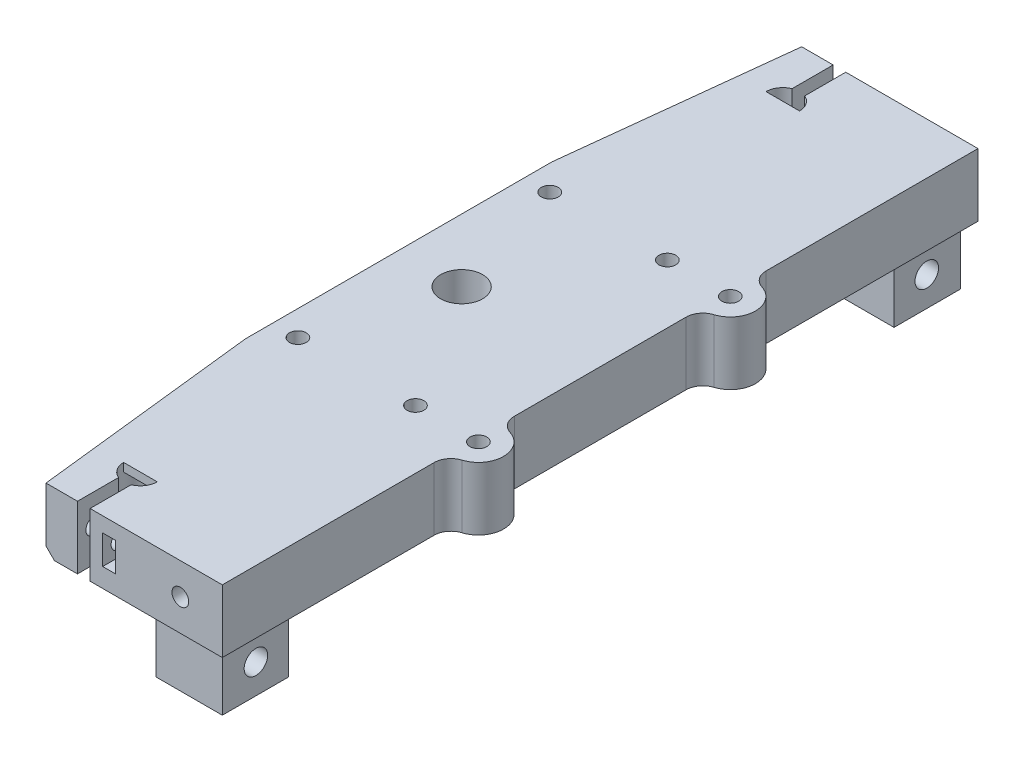
SolidWorks part; units mm, degrees
ref_plane "Płaszczyzna przednia" through (0, 0, 0) normal (0, 0, 1) x (1, 0, 0)
ref_plane "Płaszczyzna górna" through (0, 0, 0) normal (0, 1, 0) x (1, 0, 0)
ref_plane "Płaszczyzna prawa" through (0, 0, 0) normal (1, 0, 0) x (0, 0, -1)
sketch "Szkic1" plane through (0, 0, 0) normal (0, 1, 0) x (1, 0, 0)
  line L0 (-20.5, 36.5) -> (-14.5, 90)
  line L1 (27.5, -90) -> (-14.5, -90)
  line L2 (27.5, -90) -> (27.5, 90)
  line L3 (27.5, 90) -> (-14.5, 90)
  line L4 (-20.5, -36.5) -> (-20.5, 36.5)
  line L5 (27.5, 0) -> (-46.9742, 0) construction
  line L6 (-7, -80.2081) -> (-7, -90)
  line L7 (-20.5, -36.5) -> (-14.5, -90)
  line L8 (-4, -80.2081) -> (-4, -90)
  line L9 (-7, 80.2081) -> (-7, 90)
  line L10 (-4, 80.2081) -> (-4, 90)
  circle A0 centre (-14.5, 30) radius 2
  circle A1 centre (13.5, 30) radius 2
  circle A4 centre (13.5, -30) radius 2
  circle A5 centre (-14.5, -30) radius 2
  circle A6 centre (-5.5, -76.5) radius 4
  circle A7 centre (-5.5, 0) radius 5
  circle A8 centre (-5.5, 76.5) radius 4
  point P0 (0, 0)
  dimension "D7" = 6
  dimension "D10" = 4
  dimension "D11" = 30
  dimension "D12" = 15
  dimension "D13" = 10
  dimension "D16" = 8
  dimension "D1" = 48
  dimension "D2" = 180
  dimension "D3" = 27.5
  dimension "D4" = 90
  dimension "D5" = 42
  dimension "D6" = 73
  dimension "D8" = 28
  dimension "D14" = 13.5
  dimension "D15" = 15
  dimension "D17" = 3
  dimension "D19" = 13.5
  dimension "D20" = 3
extrude "Dodanie-wyciągnięcie1" add sketch "Szkic1" along normal blind 15 contours L2 L5 A7 L4 L7 L1 L6 A6 L8 A5 A4 | L5 L2 L3 L10 A8 L9 L0 L4 A7 A0 A1 region at (4.6694, 0, -43.745) region at (4.6694, 0, 43.745)
sketch "Szkic2" plane through (0, 0, 0) normal (0, -1, 0) x (1, 0, 0)
  line L0 (27.5, 90) -> (27.5, -90) construction
  line L1 (25.4, -87.9) -> (9.6, -87.9)
  line L2 (25.4, -87.9) -> (25.4, -72.1)
  line L3 (25.4, -72.1) -> (9.6, -72.1)
  line L4 (9.6, -87.9) -> (9.6, -72.1)
  line L5 (25.4, -87.9) -> (9.6, -72.1) construction
  line L6 (25.4, -72.1) -> (9.6, -87.9) construction
  line L7 (27.5, -90) -> (-4, -90) construction
  point P0 (17.5, -80)
  dimension "D1" = 15.8
  dimension "D2" = 2.1
  dimension "D3" = 2.1
extrude "Dodanie-wyciągnięcie2" add sketch "Szkic2" along normal blind 14
mirror "Lustro1" about plane through (0, 0, 0) normal (0, 0, 1) of "Dodanie-wyciągnięcie2"
sketch "Szkic3" plane through (0, 15, 0) normal (0, 1, 0) x (1, 0, 0)
  line L0 (-9.5, 76.5) -> (-1.5, 76.5)
  line L1 (-9.5, -76.5) -> (-1.5, -76.5)
  arc A0 (-7, 80.2081) -> (-4, 80.2081) centre (-5.5, 76.5) ccw construction
  arc A1 (-4, -80.2081) -> (-7, -80.2081) centre (-5.5, -76.5) ccw construction
  arc A2 (-7, 80.2081) -> (-4, 80.2081) centre (-5.5, 76.5) ccw
  arc A3 (-4, -80.2081) -> (-7, -80.2081) centre (-5.5, -76.5) ccw
  arc M7 (-4, 80.2081) -> (-7, 80.2081) centre (-5.5, 76.5) cw
  arc M15 (-7, -80.2081) -> (-4, -80.2081) centre (-5.5, -76.5) cw
extrude "Dodanie-wyciągnięcie3" add sketch "Szkic3" against normal blind 2 contours L1 M15 | L0 M7 region at (-5.5, 15, -74.8023) region at (-5.5, 15, 74.8023)
sketch "Szkic4" plane through (0, 15, 0) normal (0, 1, 0) x (1, 0, 0)
  circle A0 centre (28.5, -30) radius 2
  circle A1 centre (28.5, 30) radius 2
  circle A2 centre (13.5, 30) radius 2 construction
  circle A3 centre (13.5, -30) radius 2 construction
  circle A4 centre (13.5, 30) radius 2
  circle A5 centre (13.5, -30) radius 2
  circle A6 centre (28.5, -30) radius 6
  circle A7 centre (28.5, 30) radius 6
  line M4 (27.5, -90) -> (27.5, 90)
  dimension "D1" = 4
  dimension "D2" = 4
  dimension "D4" = 12
  dimension "D5" = 12
  dimension "D3" = 15
extrude "Dodanie-wyciągnięcie4" add sketch "Szkic4" against normal blind 15 contours A6 A0 M4 | A7 A1 M4 region at (30.8051, 15, 30) region at (30.8051, 15, -30)
sketch "Szkic5" plane through (0, 15, 0) normal (0, 1, 0) x (1, 0, 0)
  line L16 (27.5, -90) -> (27.5, -35.9161)
  line L17 (27.5, -24.0839) -> (27.5, 24.0839)
  line L18 (27.5, 35.9161) -> (27.5, 90)
  line L19 (27.5, 90) -> (-4, 90)
  line L20 (-4, 90) -> (-4, 80.2081)
  line L21 (-1.5, 76.5) -> (-9.5, 76.5)
  line L22 (-7, 80.2081) -> (-7, 90)
  line L23 (-7, 90) -> (-14.5, 90)
  line L24 (-14.5, 90) -> (-20.5, 36.5)
  line L25 (-20.5, 36.5) -> (-20.5, -36.5)
  line L26 (-20.5, -36.5) -> (-14.5, -90)
  line L27 (-14.5, -90) -> (-7, -90)
  line L28 (-7, -90) -> (-7, -80.2081)
  line L29 (-9.5, -76.5) -> (-1.5, -76.5)
  line L30 (-4, -80.2081) -> (-4, -90)
  line L31 (-4, -90) -> (27.5, -90)
  line L32 (27.5, -90) -> (27.5, -35.9161)
  line L33 (27.5, -24.0839) -> (27.5, 24.0839)
  line L34 (27.5, 35.9161) -> (27.5, 90)
  line L35 (27.5, 90) -> (-4, 90)
  line L36 (-4, 90) -> (-4, 80.2081)
  line L37 (-1.5, 76.5) -> (-9.5, 76.5)
  line L38 (-7, 80.2081) -> (-7, 90)
  line L39 (-7, 90) -> (-14.5, 90)
  line L40 (-14.5, 90) -> (-20.5, 36.5)
  line L41 (-20.5, 36.5) -> (-20.5, -36.5)
  line L42 (-20.5, -36.5) -> (-14.5, -90)
  line L43 (-14.5, -90) -> (-7, -90)
  line L44 (-7, -90) -> (-7, -80.2081)
  line L45 (-9.5, -76.5) -> (-1.5, -76.5)
  line L46 (-4, -80.2081) -> (-4, -90)
  line L47 (-4, -90) -> (27.5, -90)
  arc A0 (27.5, 28.2679) -> (27.5, 31.7321) centre (28.5, 30) ccw construction
  arc A1 (27.5, 28.2679) -> (27.5, 31.7321) centre (28.5, 30) ccw
  arc A2 (27.5, -31.7321) -> (27.5, -28.2679) centre (28.5, -30) ccw construction
  arc A3 (27.5, -31.7321) -> (27.5, -28.2679) centre (28.5, -30) ccw
  circle A4 centre (28.5, 30) radius 2
  circle A5 centre (28.5, -30) radius 2
  arc A6 (27.5, -35.9161) -> (27.5, -24.0839) centre (28.5, -30) ccw
  arc A7 (27.5, 24.0839) -> (27.5, 35.9161) centre (28.5, 30) ccw
  arc A8 (-1.5, 76.5) -> (-4, 80.2081) centre (-5.5, 76.5) ccw
  arc A9 (-7, 80.2081) -> (-9.5, 76.5) centre (-5.5, 76.5) ccw
  arc A10 (-9.5, -76.5) -> (-7, -80.2081) centre (-5.5, -76.5) ccw
  arc A11 (-4, -80.2081) -> (-1.5, -76.5) centre (-5.5, -76.5) ccw
  arc A12 (27.5, -35.9161) -> (27.5, -24.0839) centre (28.5, -30) ccw
  arc A13 (27.5, 24.0839) -> (27.5, 35.9161) centre (28.5, 30) ccw
  arc A14 (-1.5, 76.5) -> (-4, 80.2081) centre (-5.5, 76.5) ccw
  arc A15 (-7, 80.2081) -> (-9.5, 76.5) centre (-5.5, 76.5) ccw
  arc A16 (-9.5, -76.5) -> (-7, -80.2081) centre (-5.5, -76.5) ccw
  arc A17 (-4, -80.2081) -> (-1.5, -76.5) centre (-5.5, -76.5) ccw
  arc M23 (27.5, 31.7321) -> (27.5, 28.2679) centre (28.5, 30) cw
  line M24 (27.5, 28.2679) -> (27.5, 31.7321)
  arc M25 (27.5, -28.2679) -> (27.5, -31.7321) centre (28.5, -30) cw
  line M26 (27.5, -31.7321) -> (27.5, -28.2679)
  dimension "D2" = 4
  dimension "D3" = 4
  dimension "D1" = 0
extrude "Wytnij-wyciągnięcie1" cut sketch "Szkic5" against normal blind 15 contours M25 M26 | A5 M26 | A4 M24 | M23 M24 region at (28.8427, 15, -30) region at (27.09, 15, -30) region at (28.8427, 15, 30) region at (27.09, 15, 30)
fillet "Zaokrąglenie1" radius 4 4 edges at (27.5, 7.5, -35.9161) (27.5, 7.5, -24.0839) (27.5, 7.5, 24.0839) (27.5, 7.5, 35.9161)
chamfer "Sfazowanie1" distance 2 angle 45 3 edges at (-17.5, 0, -63.25) (-17.5, 0, 63.25) (-20.5, 0, 0)
sketch "Szkic8" plane through (-4, 0, 0) normal (-1, 0, 0) x (0, 0, 1)
  line L0 (90, 15) -> (90, 0) construction
  line L1 (80.2081, 15) -> (90, 15) construction
  circle A0 centre (86, 8) radius 2
  dimension "D1" = 4
  dimension "D2" = 4
  dimension "D3" = 7
extrude "Wytnij-wyciągnięcie3" cut sketch "Szkic8" along normal through all and the other way blind 7
sketch "Szkic9" plane through (-4, 0, 0) normal (-1, 0, 0) x (0, 0, 1)
  circle A0 centre (86, 8) radius 3.5
  dimension "D1" = 7
extrude "Wytnij-wyciągnięcie4" cut sketch "Szkic9" along normal blind 4 from offset 8
sketch "Szkic10" plane through (-4, 0, 0) normal (-1, 0, 0) x (0, 0, 1)
  line L0 (86, 11.4641) -> (90, 11.4641)
  line L1 (86, 11.4641) -> (83, 9.7321)
  line L2 (83, 9.7321) -> (83, 6.2679)
  line L3 (83, 6.2679) -> (86, 4.5359)
  line L4 (86, 4.5359) -> (89, 6.2679)
  line L5 (89, 6.2679) -> (89, 9.7321)
  line L6 (89, 9.7321) -> (86, 11.4641)
  line L7 (90, 15) -> (90, 0) construction
  line L8 (90, 11.4641) -> (90, 4.5359)
  line L9 (90, 4.5359) -> (86, 4.5359)
  circle A0 centre (86, 8) radius 3 construction
  circle M1 centre (86, 8) radius 2
  line M3 (90, 0) -> (90, 15)
  dimension "D1" = 6
extrude "Wytnij-wyciągnięcie5" cut sketch "Szkic10" against normal blind 3 from offset 3 contours L5 L6 L1 L2 L3 L4 M1 | L9 L0 L6 L5 L4 M3 region at (-4, 10.5187, 87.4542) region at (-4, 11.3841, 88) offset against normal yes
mirror "Lustro2" about plane through (0, 0, 0) normal (0, 0, 1) of "Wytnij-wyciągnięcie5", "Wytnij-wyciągnięcie4", "Wytnij-wyciągnięcie3"
sketch "Szkic11" plane through (0, 0, 90) normal (0, 0, 1) x (1, 0, 0)
  line L0 (27.5, 15) -> (27.5, 0) construction
  line L1 (27.5, 15) -> (-4, 15) construction
  circle A0 centre (17.5, 7.5) radius 2
  point P4 (27.5, 7.5)
  dimension "D1" = 4
  dimension "D2" = 10
  dimension "D3" = 7.5
extrude "Wytnij-wyciągnięcie6" cut sketch "Szkic11" against normal blind 7
mirror "Lustro3" about plane through (0, 0, 0) normal (0, 0, 1) of "Wytnij-wyciągnięcie6"
sketch "Szkic12" plane through (25.4, 0, 0) normal (1, 0, 0) x (0, 0, -1)
  line L0 (-87.9, -14) -> (-87.9, 0) construction
  line L1 (-87.9, -14) -> (-72.1, -14) construction
  line L2 (87.9, -14) -> (87.9, 0) construction
  circle A0 centre (-79.9, -7) radius 2.8
  circle A1 centre (79.9, -7) radius 2.8
  dimension "D1" = 5.6
  dimension "D3" = 7
  dimension "D4" = 8
  dimension "D2" = 8
extrude "Wytnij-wyciągnięcie7" cut sketch "Szkic12" against normal through all
